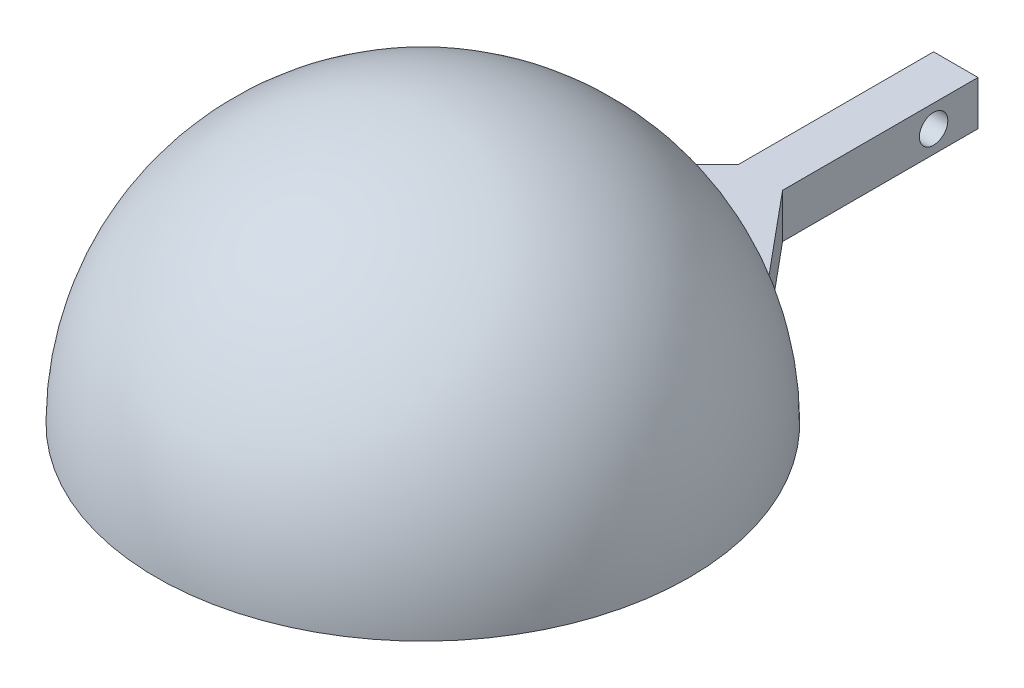
SolidWorks part; units mm, degrees
ref_plane "Front Plane" through (0, 0, 0) normal (0, 0, 1) x (1, 0, 0)
ref_plane "Top Plane" through (0, 0, 0) normal (0, 1, 0) x (1, 0, 0)
ref_plane "Right Plane" through (0, 0, 0) normal (1, 0, 0) x (0, 0, -1)
sketch "Sketch2" plane through (0, 0, 0) normal (0, 0, 1) x (1, 0, 0)
  line L0 (0, 29) -> (0, 30)
  line L1 (29, 0) -> (30, 0)
  line L2 (0, 0) -> (0, 30) construction
  circle A0 centre (0, 0) radius 30 construction
  arc A1 (0, 30) -> (30, 0) centre (0, 0) cw
  arc A2 (0, 29) -> (29, 0) centre (0, 0) cw
  dimension "D1" = 60
  dimension "D2" = 1
revolve "Revolve1" add sketch "Sketch2" angle 360 about L2
sketch "Sketch3" plane through (0, 0, 0) normal (0, -1, 0) x (1, 0, 0)
  line L0 (0, -30) -> (0, -60) construction
  line L1 (-2.039, -38) -> (6.2568, -38) construction
  line L2 (-2.5, -60) -> (2.5, -60)
  line L3 (-2.5, -60) -> (-2.5, -30)
  line L4 (-2.5, -30) -> (2.5, -30)
  line L5 (2.5, -60) -> (2.5, -30)
  line L6 (-2.5, -38) -> (2.5, -38)
  line L8 (2.5, -38) -> (12.2228, -26.308)
  line L9 (12.2228, -26.308) -> (12.2191, -26.3001)
  line L10 (-2.5, -38) -> (-14.4183, -26.308)
  line L11 (-14.4183, -26.308) -> (-13.9377, -25.4311)
  circle A0 centre (0, 0) radius 30 construction
  circle A1 centre (0, 0) radius 30 construction
  circle A2 centre (0, 0) radius 29 construction
  arc A3 (-13.9377, -25.4311) -> (12.2191, -26.3001) centre (-0.0374, -1.1251) ccw
  point P9 (0, -60)
  circle M2 centre (0, 0) radius 30
  circle M3 centre (0, 0) radius 29
  dimension "D1" = 30
  dimension "D2" = 8
  dimension "D3" = 5
extrude "Boss-Extrude1" add sketch "Sketch3" against normal blind 5 contours L10 L3 L4 M2 | L3 L6 L5 L4 | L5 L8 L4 M2 | L6 L3 L2 L5 | L11 L9 M2 M3 region at (0, 0, -49) region at (-6.203, 0, -31.7836) region at (0, 0, -34) region at (5.1926, 0, -32.1094) region at (-13.941, 0, -25.9994)
sketch "Sketch4" plane through (2.5, 0, 0) normal (1, 0, 0) x (0, 0, -1)
  line L0 (60, 2.5) -> (41.7869, 2.5) construction
  line L1 (60, 5) -> (60, 0) construction
  circle A0 centre (55, 2.5) radius 1.6
  dimension "D1" = 3.2
  dimension "D2" = 5
extrude "Cut-Extrude1" cut sketch "Sketch4" against normal through all
sketch "Sketch5" plane through (0, 0, 0) normal (0, 1, 0) x (1, 0, 0)
  line L0 (0, -29) -> (0, 29) construction
  line L1 (29, 0) -> (-29, 0) construction
  line L3 (1, -22.5) -> (-1, -22.5)
  line L4 (1, -22.5) -> (1, 22.5)
  line L5 (1, 22.5) -> (-1, 22.5)
  line L6 (-1, -22.5) -> (-1, 22.5)
  line L7 (22.5, -1.0087) -> (-22.5, -1.0087)
  line L8 (22.5, -1.0087) -> (22.5, 0.9913)
  line L9 (22.5, 0.9913) -> (-22.5, 0.9913)
  line L10 (-22.5, -1.0087) -> (-22.5, 0.9913)
  circle A0 centre (0, 0) radius 29 construction
  point P11 (0, -22.5)
  point P12 (-1, 0)
  point P18 (0, -1.0087)
  dimension "D1" = 2
  dimension "D2" = 45
  dimension "D3" = 2
  dimension "D4" = 45
extrude "Boss-Extrude2" add sketch "Sketch5" along normal up to surface (18.2683 mm away) contours L9 L10 L7 L8 | L4 L5 L6 L3 up to face at (0, 0, -29)
sketch "Sketch7" plane through (0, 0, -22.5) normal (0, 0, -1) x (-1, 0, 0)
  line L0 (1, 18.2688) -> (1, 0) construction
  line L1 (-1, 0) -> (1, 0)
  line L2 (-1, 0) -> (-1, 3)
  line L3 (-1, 3) -> (1, 3)
  line L4 (1, 0) -> (1, 3)
  dimension "D1" = 3
extrude "Boss-Extrude3" add sketch "Sketch7" along normal up to surface (6.4828 mm away) up to face at (0, 0, -29)
ref_point "Point1"
ref_axis "Axis1" through (0, 0, 0) along (0, -1, 0)
pattern_circular "CirPattern1" count 4 over 360 about axis through (0, 0, 0) along (0, -1, 0) of "Boss-Extrude3"
